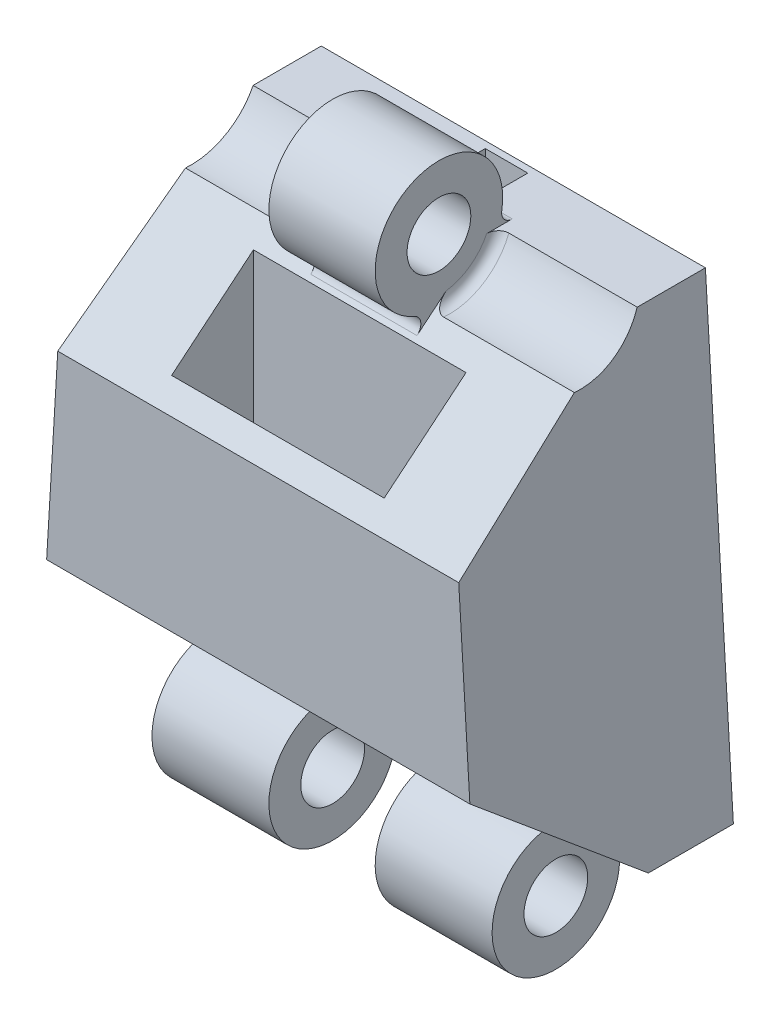
SolidWorks part; units mm, degrees
ref_plane "Front Plane" through (0, 0, 0) normal (0, 0, 1) x (1, 0, 0)
ref_plane "Top Plane" through (0, 0, 0) normal (0, 1, 0) x (1, 0, 0)
ref_plane "Right Plane" through (0, 0, 0) normal (1, 0, 0) x (0, 0, -1)
sketch "Sketch1" plane through (0, 0, 0) normal (0, 0, 1) x (1, 0, 0)
  line L0 (-56.5743, 0) -> (-35.8731, 0)
  line L1 (-55.2587, 22) -> (-37.1887, 22)
  line L2 (-56.5743, 0) -> (-55.2587, 22)
  line L3 (-35.8731, 0) -> (-37.1887, 22)
extrude "Boss-Extrude1" add sketch "Sketch1" along normal blind 12
sketch "Sketch2" plane through (0, 0, 12) normal (0, 0, 1) x (1, 0, 0)
  line L0 (-35.8731, 0) -> (-56.5743, 0)
  line L1 (-46.2237, 0) -> (-46.2237, 29.5391)
ref_plane "Plane1" through (-46.2237, 0, 0) normal (1, 0, 0) x (0, 0, -1)
sketch "Sketch3" plane through (-46.2237, 0, 0) normal (1, 0, 0) x (0, 0, -1)
  line L0 (0, 0) -> (-4, 0)
  line L1 (-12, 0) -> (0, 0) construction
  line L2 (-4, 0) -> (-12, 6.614)
  line L3 (-12, 0) -> (-12, 22) construction
  line L4 (-12, 6.614) -> (-12, 0)
  line L5 (-12, 0) -> (-4, 0)
extrude "Cut-Extrude1" cut sketch "Sketch3" against normal through all both and the other way through all contours L4 L5 L2 region at (-46.2237, 2.2047, 9.3333)
sketch "Sketch6" plane through (-46.2237, 0, 0) normal (1, 0, 0) x (0, 0, -1)
  line L1 (0, 0) -> (-12, 0)
  line L2 (-6, 0) -> (-6, -1.1)
  circle A0 centre (-6, -1.1) radius 1.5
  circle A1 centre (-6, -1.1) radius 3
extrude "Boss-Extrude2" add sketch "Sketch6" along normal mid plane 16 contours L1 A1 A0 | L1 A1 A0 region at (-46.2237, -0.5537, 3.1241) region at (-46.2237, 0.8343, 6)
extrude "Cut-Extrude2" cut sketch "Sketch6<3>" against normal mid plane 5 contours L1 A1 A0 | L1 A1 A0 region at (-46.2237, -0.5537, 3.1241) region at (-46.2237, 0.8343, 6)
sketch "Sketch6<3>" plane through (-46.2237, 0, 0) normal (1, 0, 0) x (0, 0, -1) same geometry as "Sketch6"
sketch "Sketch8" plane through (-46.2237, 0, 0) normal (1, 0, 0) x (0, 0, -1)
  line L0 (0, 22) -> (-4, 22)
  line L1 (-12, 22) -> (0, 22) construction
  line L2 (-4, 22) -> (-12, 15.3704)
  line L3 (-12, 6.614) -> (-12, 22) construction
  line L4 (-12, 15.3704) -> (-12, 22)
  line L5 (-12, 22) -> (-4, 22)
extrude "Cut-Extrude3" cut sketch "Sketch8" against normal through all both and the other way through all contours L5 L4 L2 region at (-46.2237, 19.7901, 9.3333)
sketch "Sketch9" plane through (-46.2237, 0, 0) normal (1, 0, 0) x (0, 0, -1)
  line L0 (-12, 15.3704) -> (-12, 26.5168)
  line L1 (0, 22) -> (-12, 22)
  line L2 (-6, 22) -> (-6, 23.1)
  circle A0 centre (-6, 23.1) radius 1.5
  circle A1 centre (-6, 23.1) radius 3
extrude "Boss-Extrude3" add sketch "Sketch9" along normal mid plane 5 contours L1 A1 A0 | L1 A1 A0 region at (-46.2237, 21.1657, 6) region at (-46.2237, 22.0727, 4.0946)
sketch "Sketch11" plane through (-43.7237, 0, 0) normal (1, 0, 0) x (0, 0, -1)
  circle A0 centre (-6, 23.1) radius 3
extrude "Cut-Extrude4" cut sketch "Sketch11" along normal blind 10
sketch "Sketch12" plane through (-48.7237, 0, 0) normal (-1, 0, 0) x (0, 0, 1)
  circle A0 centre (6, 23.1) radius 3
extrude "Cut-Extrude5" cut sketch "Sketch12" along normal blind 10
fillet "Fillet1" radius 0.5 2 edges at (-46.2237, 22, 3.2089) (-46.2237, 20.1128, 6.2772)
fillet "Fillet2" radius 0.5 2 edges at (-48.7237, 20.5446, 4.4283) (-43.7237, 20.5446, 4.4283)
sketch "Sketch13" plane through (0, 15.008, 12.4372) normal (0, 0.77, 0.6381) x (1, 0, 0)
  line L0 (-46.2237, 0.5678) -> (-46.2237, 1.7678)
  line L1 (-55.6551, 0.5678) -> (-36.7922, 0.5678) construction
  line L2 (-46.2237, 1.7678) -> (-41.2237, 1.7678)
  line L3 (-41.2237, 1.7678) -> (-41.2237, 6.7678)
  line L4 (-41.2237, 6.7678) -> (-51.2237, 6.7678)
  line L5 (-51.2237, 6.7678) -> (-51.2237, 1.7678)
  line L6 (-51.2237, 1.7678) -> (-46.2237, 1.7678)
ref_plane "Plane2" through (0, 10, 0) normal (0, 1, 0) x (1, 0, 0)
sketch "Sketch14" plane through (0, 10, 0) normal (0, 1, 0) x (1, 0, 0)
  line L0 (-51.2237, -7.2262) -> (-51.2237, -11.076)
  line L1 (-51.2237, -11.076) -> (-41.2237, -11.076)
  line L2 (-41.2237, -11.076) -> (-41.2237, -7.2262)
  line L3 (-41.2237, -7.2262) -> (-51.2237, -7.2262)
extrude "Cut-Extrude6" cut sketch "Sketch14" against normal up to surface and the other way up to surface up to face at (-46.2237, 2.0775, 6.5128) other way up to face at (-46.2124, 19.1095, 7.4879)
sketch "Sketch15" plane through (-46.2237, 0, 0) normal (1, 0, 0) x (0, 0, -1)
  line L0 (0, 22) -> (-2.32, 22)
  line L1 (-3.2089, 22) -> (0, 22) construction
  line L2 (-2.32, 22) -> (-2.32, -4.365)
  line L3 (-2.32, -4.365) -> (-0.32, -4.365)
  line L4 (-0.32, -4.365) -> (-0.32, 22)
extrude "Cut-Extrude7" cut sketch "Sketch15" against normal mid plane 2 contours L3 L4 L0 L2 region at (-46.2237, 8.8175, 1.32)
